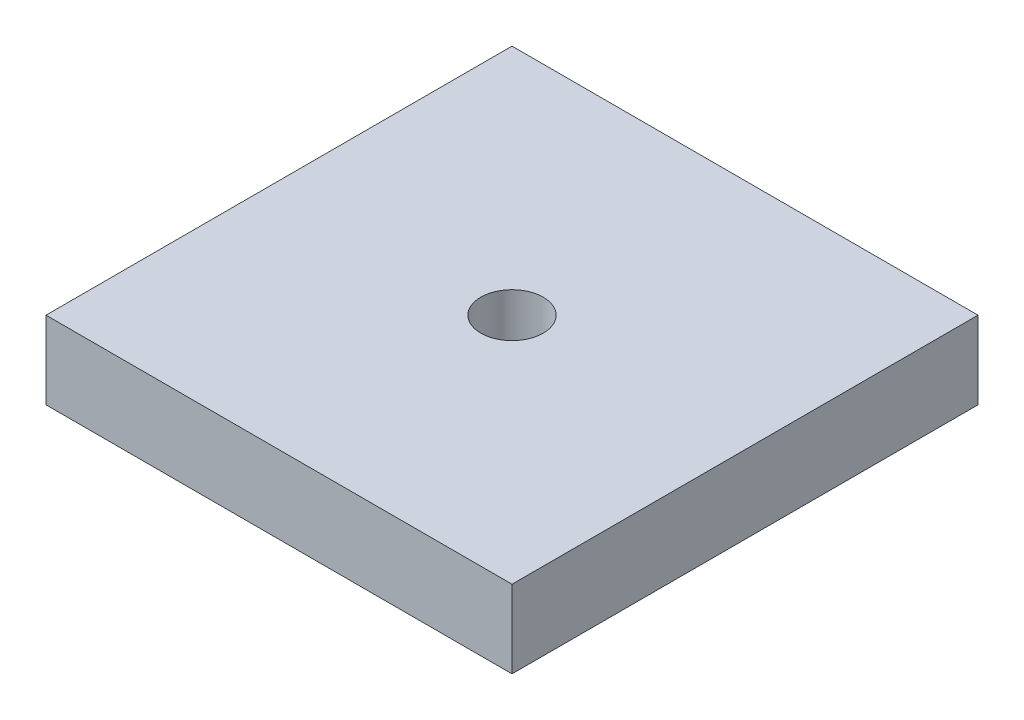
SolidWorks part; units mm, degrees
ref_plane "Front" through (0, 0, 0) normal (0, 0, 1) x (1, 0, 0)
ref_plane "Top" through (0, 0, 0) normal (0, 1, 0) x (1, 0, 0)
ref_plane "Right" through (0, 0, 0) normal (1, 0, 0) x (0, 0, -1)
sketch "Sketch1" plane through (0, 0, 0) normal (0, 1, 0) x (1, 0, 0)
  line L1 (0, 0) -> (38.1, 0)
  line L2 (0, 0) -> (0, 38.1)
  line L3 (0, 38.1) -> (38.1, 38.1)
  line L4 (38.1, 0) -> (38.1, 38.1)
  dimension "D1" = 38.1
extrude "Boss-Extrude1" add sketch "Sketch1" along normal blind 6.35
sketch "Sketch4" plane through (0, 6.35, 0) normal (0, 1, 0) x (1, 0, 0)
  line L0 (0, 38.1) -> (38.1, 0) construction
  point P0 (19.05, 19.05)
  point P9 (19.05, 19.05)
hole_wizard "1/4-20 Tapped Hole1" positions "Sketch4" profile "Sketch3" tap size "1/4-20" standard "ANSI Inch"
sketch "Sketch3" plane through (19.05, 6.35, -19.05) normal (1, 0, 0) x (0, 0, 1)
  line L0 (0, 0) -> (0, 18.0438)
  line L1 (0, 18.0438) -> (2.5527, 16.51)
  line L2 (2.5527, 16.51) -> (2.5527, 0)
  line L5 (2.5527, 0) -> (0, 0)
  line L10 (0, 18.0438) -> (-2.5527, 16.51) construction
  line L11 (0, -6.35) -> (0, 107.95) construction
  dimension "Tap Drill Dia." = 5.1054
  dimension "Tap Drill Depth" = 16.51
  dimension "Drill Angle" = 118
cosmetic thread "Hole Thread1" parameters "D1"=12.7, "D2"=6.35
